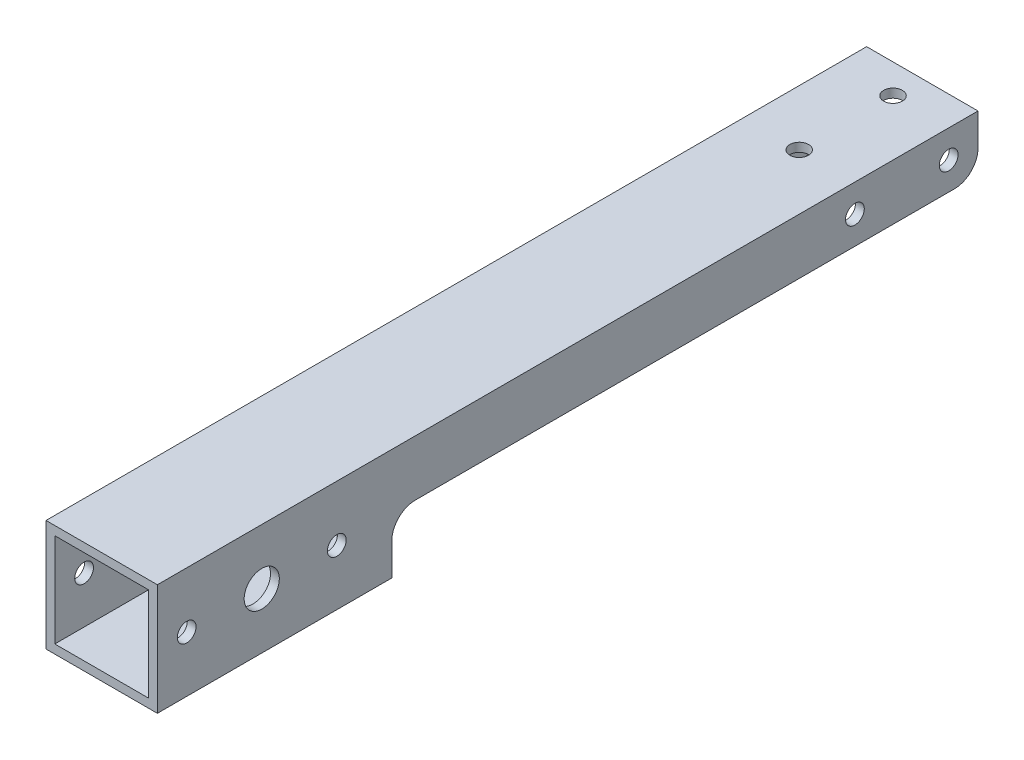
SolidWorks part; units mm, degrees
material "Gerais  - 6061-T6"
ref_plane "Plano frontal" through (0, 0, 0) normal (0, 0, 1) x (1, 0, 0)
ref_plane "Plano superior" through (0, 0, 0) normal (0, 1, 0) x (1, 0, 0)
ref_plane "Plano direito" through (0, 0, 0) normal (1, 0, 0) x (0, 0, -1)
sketch "Esboço1" plane through (0, 0, 0) normal (0, 0, 1) x (1, 0, 0)
  line L1 (-9.5, -9.5) -> (9.5, -9.5)
  line L2 (-9.5, -9.5) -> (-9.5, 9.5)
  line L3 (-9.5, 9.5) -> (9.5, 9.5)
  line L4 (9.5, -9.5) -> (9.5, 9.5)
  line L5 (0, 9.5) -> (0, -9.5) construction
  line L6 (-9.5, 0) -> (9.5, 0) construction
  line L7 (8, -8) -> (-8, -8)
  line L8 (8, -8) -> (8, 8)
  line L9 (8, 8) -> (-8, 8)
  line L10 (-8, -8) -> (-8, 8)
  line L11 (0, 8) -> (0, -8) construction
  line L12 (8, 0) -> (-8, 0) construction
  point P0 (0, 0)
  point P4 (0, 0)
  dimension "D1" = 19
  dimension "D2" = 1.5
extrude "Ressalto-extrusão1" add sketch "Esboço1" along normal blind 140 contours L3 L4 L1 L2 | L8 L7 L10 L9
sketch "Esboço2" plane through (9.5, 0, 0) normal (1, 0, 0) x (0, 0, -1)
  line L0 (-161.3966, 22.4643) -> (-181.3966, 6.4643) construction
  line L1 (0, -9.5) -> (0, 9.5) construction
  line L2 (-161.3966, 6.4643) -> (-181.3966, 6.4643) construction
  line L3 (-161.3966, 6.4643) -> (-161.3966, 22.4643) construction
  line L4 (-161.3966, 22.4643) -> (-181.3966, 22.4643) construction
  line L5 (-181.3966, 6.4643) -> (-181.3966, 22.4643) construction
  line L6 (-171.3966, 22.4643) -> (-171.3966, 6.4643) construction
  line L7 (-161.3966, 14.4643) -> (-181.3966, 14.4643) construction
  line L8 (-135, 0) -> (-109.3875, 0) construction
  line L9 (-140, -9.5) -> (-140, 9.5) construction
  line L10 (-12.0679, 0) -> (-12.0679, 9.5) construction
  line L11 (-140, 9.5) -> (0, 9.5) construction
  circle A5 centre (-135, 0) radius 1.6
  circle A6 centre (-122.1938, 0) radius 3
  circle A7 centre (-109.3875, 0) radius 1.6
  circle A8 centre (-5, 4.75) radius 1.6
  circle A9 centre (-21, 4.75) radius 1.6
  point P6 (-171.3966, 14.4643)
  point P13 (-140, 0)
  point P24 (-12.0679, 4.75)
  dimension "D1" = 6
  dimension "D5" = 3.2
  dimension "D8" = 3.2
  dimension "D2" = 16
  dimension "D3" = 20
  dimension "D4" = 5
  dimension "D6" = 16
  dimension "D7" = 5
extrude "Corte-extrusão1" cut sketch "Esboço2" against normal through all contours A7 | A5 | A6 | A8 | A9 region at (9.5, 0, 135) region at (9.5, 0, 109.3875)
sketch "Esboço3" plane through (0, 9.5, 0) normal (0, 1, 0) x (1, 0, 0)
  line L0 (0, -21) -> (0, -5) construction
  line L1 (-9.5, 0) -> (9.5, 0) construction
  circle A1 centre (0, -21) radius 1.6
  circle A2 centre (0, -5) radius 1.6
  dimension "D2" = 3.2
  dimension "D1" = 16
  dimension "D4" = 5
extrude "Corte-extrusão2" cut sketch "Esboço3" against normal up to surface (1.5 mm away) up to face at (0, 8, 70)
sketch "Esboço5" plane through (0, 0, 0) normal (0, 0, -1) x (-1, 0, 0)
  line L0 (-9.5, -9.5) -> (-9.5, 9.5) construction
  line L1 (9.5, -9.5) -> (-9.5, -9.5)
  line L2 (9.5, -9.5) -> (9.5, 0)
  line L3 (9.5, 0) -> (-9.5, 0)
  line L4 (-9.5, -9.5) -> (-9.5, 0)
extrude "Corte-extrusão4" cut sketch "Esboço5" against normal offset from surface (100 mm away) 40 up to face at (0, 0, 140)
fillet "Filete1" radius 4 4 edges at (-8.75, 0, 100) (8.75, 0, 100) (-8.75, 0, 0) (8.75, 0, 0)
